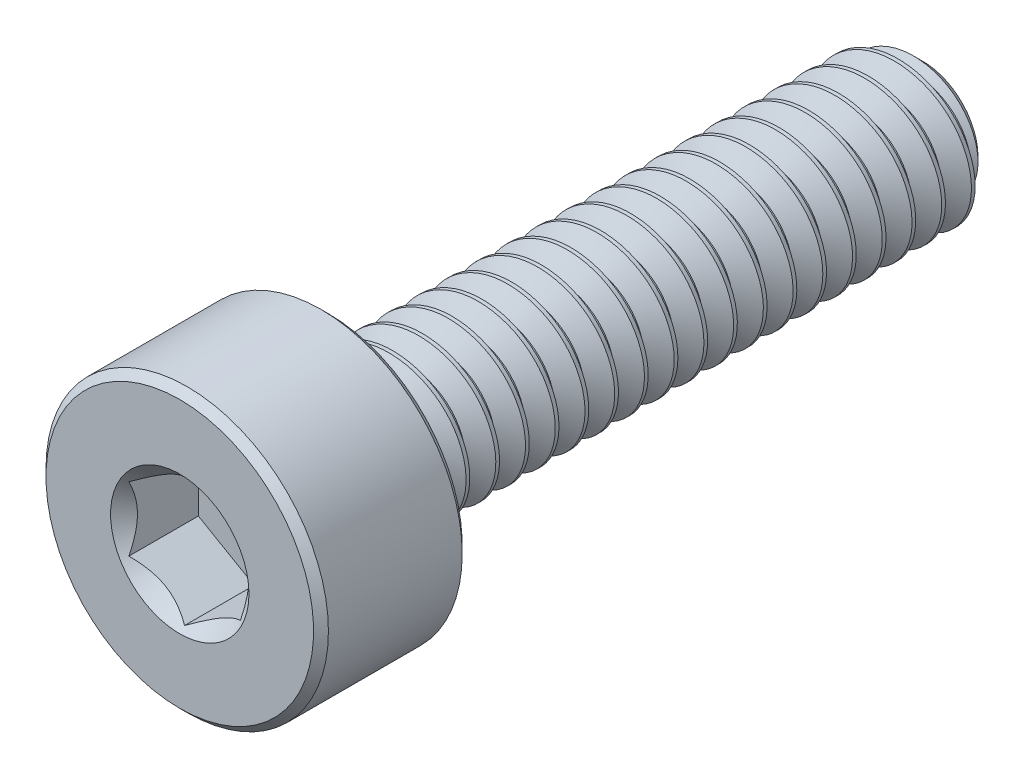
SolidWorks part; units mm, degrees
ref_plane "Front Plane" through (0, 0, 0) normal (0, 0, 1) x (1, 0, 0)
ref_plane "Top Plane" through (0, 0, 0) normal (0, 1, 0) x (1, 0, 0)
ref_plane "Right Plane" through (0, 0, 0) normal (1, 0, 0) x (0, 0, -1)
sketch "Sketch1" plane through (0, 0, 0) normal (1, 0, 0) x (0, 0, -1)
  line L0 (-5, 0) -> (5, 0) construction
  line L1 (5, 0) -> (5, 0.7402) construction
  line L2 (5, 0.7402) -> (4.7402, 1) construction
  line L3 (4.7402, 1) -> (4.7, 1) construction
  line L4 (4.7, 1) -> (-3, 1) construction
  line L5 (-3, 1) -> (-3, 1.9) construction
  line L6 (-3, 1.9) -> (-5, 1.9) construction
  line L7 (-5, 1.9) -> (-5, 0) construction
  line L8 (5, 0.7402) -> (5, 1) construction
  line L9 (4.975, 1.0433) -> (5.175, 0.6969) construction
  line L10 (5.175, 0.6969) -> (5.375, 1.0433) construction
  line L11 (5.375, 1.0433) -> (4.975, 1.0433) construction
  line L12 (5.175, 1.0433) -> (5.175, 1) construction
  line L13 (5.175, 0.6969) -> (5.175, 0.7402) construction
  line L14 (5.15, 0.7402) -> (5.2, 0.7402) construction
  line L15 (5, 1) -> (5.35, 1) construction
  line L16 (4.9875, 1.0217) -> (5.3625, 1.0217) construction
  line L17 (5, 0) -> (5, -1) construction
  line L18 (-3.1, 1.9) -> (-3, 1.8) construction
  line L19 (-4.9, 1.9) -> (-5, 1.8) construction
  line L20 (-3, 1) -> (-3, 0) construction
  line L21 (-3, 0.5) -> (-0.3333, 0.5) construction
  line L22 (-0.3333, 0.5) -> (2.3333, 0.5) construction
  line L23 (2.3333, 0.5) -> (5, 0.5) construction
  line L24 (-0.3333, 0.5) -> (-0.3333, 1) construction
  line L25 (-0.3333, 1) -> (-0.3333, 1.9) construction
  line L26 (2.3333, 0.5) -> (2.3333, 1.9) construction
  point P0 (-5, 0.75)
  point P3 (4, 1)
  point P4 (0, 0)
  point P18 (2.3333, 1)
  point P22 (5.175, 0.7402)
  point P24 (4.7, 1)
  point P25 (5.175, 1)
  point P28 (5.175, 1.0217)
  point P29 (4, -1)
  point P30 (-0.3333, 1)
  point P31 (-4, 1.9)
  point P37 (-3.35, 1.9)
  point P38 (-4.85, 1.9)
  point P45 (-0.3333, 0.5)
  point P46 (2.3333, 0.5)
  dimension "D2" = 0.05
  dimension "D7" = 0.1
  dimension "D8" = 0.1
  dimension "D9" = 0.1
  dimension "D10" = 0.05
  dimension "D11" = 0.25
  dimension "Drive Size" = 1.5
  dimension "Head Diameter" = 3.8
  dimension "Head Height" = 2
  dimension "Thread Pitch" = 0.4
  dimension "Thread Size" = 2
  dimension "Length" = 8
  dimension "D12" = 0.3
  dimension "D4" = 1
  dimension "D3" = 45
sketch "Sketch2" plane through (0, 0, 0) normal (1, 0, 0) x (0, 0, -1)
  line L0 (-5, 0) -> (-5, 1.8)
  line L1 (-4.9, 1.9) -> (-3.1, 1.9)
  line L2 (-3, 1.8) -> (-3, 1.1)
  line L4 (4.7402, 1) -> (5, 0.7402)
  line L5 (5, 0.7402) -> (5, 0)
  line L6 (-3, 1.9) -> (-5, 1.9) construction
  line L7 (5, 0) -> (-5, 0)
  line L8 (-4.9, 1.9) -> (-5, 1.8) construction
  line L10 (-4.9, 1.9) -> (-5, 1.8)
  line L14 (-3.1, 1.9) -> (-3, 1.8) construction
  line L16 (-3.1, 1.9) -> (-3, 1.8)
  line L17 (-3, 1) -> (-3, 1.9) construction
  line L19 (-2.9, 1) -> (4.7402, 1)
  line L20 (4.7, 1) -> (-3, 1) construction
  arc A1 (-3, 1.1) -> (-2.9, 1) centre (-2.9, 1.1) ccw
  dimension "D3" = 0.1
revolve "Revolve1" add sketch "Sketch2" angle 360 about L7
sketch "Sketch3" plane through (0, 0, 5) normal (0, 0, 1) x (1, 0, 0)
  line L1 (0.75, -0.433) -> (0.75, 0.433)
  line L2 (0.75, 0.433) -> (0, 0.866)
  line L3 (0, 0.866) -> (-0.75, 0.433)
  line L4 (-0.75, 0.433) -> (-0.75, -0.433)
  line L5 (-0.75, -0.433) -> (0, -0.866)
  line L6 (0, -0.866) -> (0.75, -0.433)
  circle A0 centre (0, 0) radius 0.75 construction
  circle A1 centre (0, 0) radius 1.9 construction
  circle A2 centre (0, 0) radius 1.9 construction
  circle A3 centre (0, 0) radius 0.866 construction
  point P13 (0, 0)
  dimension "D1" = 1.7321
extrude "Cut-Extrude1" cut sketch "Sketch3" against normal offset from surface (1 mm away) 1 up to face at (0, 1.8, 3)
sketch "Sketch4" plane through (0, 0, 5) normal (0, 0, 1) x (1, 0, 0)
  circle A0 centre (0, 0) radius 0.931
  dimension "D1" = 1.862
extrude "Cut-Extrude2" cut sketch "Sketch4" against normal up to vertex (1 mm away) draft 45 up to point (0, 1.9, 4)
sketch "Sketch11" plane through (0, 0, 0) normal (1, 0, 0) x (0, 0, -1)
  line L0 (-5, 0) -> (5, 0) construction
  line L1 (-5, 0) -> (5, 0) construction
  line L2 (-1.5, 0) -> (-1.5, 1) construction
  line L3 (4.7, 1) -> (-3, 1) construction
  line L4 (3.5, 0) -> (3.5, 1) construction
  line L6 (5, 0.7402) -> (5, 1) construction
  point P2 (-1.5, 0)
  point P3 (3.5, 0)
  dimension "D1" = 1.5
  dimension "D2" = 1.5
sketch "Sketch6" plane through (0, 0, -5) normal (0, 0, -1) x (-1, 0, 0)
  circle A0 centre (0, 0) radius 1
curve "Helix/Spiral1" pitch 0.4 height 8.4 radius 1 centre (0, 0, -5) axis (0, 0, 1) start towards (0, 1, 0)
sketch "Sketch10" plane through (0, 0, 0) normal (1, 0, 0) x (0, 0, -1)
  line L0 (-2.9, -1.9) -> (-2.9, 1.9)
  line L5 (-5, 0) -> (5, 0) construction
  line L6 (-2.9, 1) -> (-2.9, -1) construction
  point P3 (-2.9, 0)
split "Split1" trim tools "Sketch10" bodies to split 106 resulting bodies 114 115
sketch "Sketch7" plane through (0, 0, 0) normal (1, 0, 0) x (0, 0, -1)
  line L0 (4.9875, 1.0217) -> (5.3625, 1.0217)
  line L1 (5.3625, 1.0217) -> (5.2, 0.7402)
  line L2 (5.2, 0.7402) -> (5.15, 0.7402)
  line L3 (5.15, 0.7402) -> (4.9875, 1.0217)
sweep "Cut-Sweep1" cut profiles "Sketch7" path "Helix/Spiral1" align with end faces yes
sketch "Sketch8" plane through (0, 0, 0) normal (1, 0, 0) x (0, 0, -1)
  line L0 (-3, 0) -> (-3, 1)
  line L1 (-2.9, -1) -> (-2.9, 1) construction
  line L2 (-3, 1) -> (-2.9, 1)
  line L4 (-2.9, 1) -> (-2.3226, 0)
  line L5 (-2.3226, 0) -> (-3, 0)
  line L6 (4.7, 1) -> (-3, 1) construction
  line L7 (-5, 0) -> (5, 0) construction
  dimension "D1" = 60
revolve "Revolve2" add sketch "Sketch8" angle 360 about L5
equation "\"D2@Sketch1\" = \"Thread Pitch@Sketch1\" / 8"
equation "\"D4@Helix/Spiral1\" = \"Thread Pitch@Sketch1\""
equation "\"D7@Sketch1\" = \"Head Height@Sketch1\" * .05"
equation "\"D8@Sketch1\"=\"D7@Sketch1\""
equation "\"D9@Sketch1\"=\"D7@Sketch1\""
equation "\"D10@Sketch1\"=\"D7@Sketch1\"/2"
equation "\"D11@Sketch1\"=\"D10@Sketch1\"*5"
equation "\"D4@Sketch1\"=\"Thread Pitch@Sketch1\"*2.5"
equation "\"D12@Sketch1\"=\"Thread Pitch@Sketch1\"*.75"
equation "\"D3@Helix/Spiral1\"=\"Length@Sketch1\"+\"Thread Pitch@Sketch1\""
equation "\"D3@Sketch2\"=\"Thread Size@Sketch1\"*0.05"
equation "\"D1@Sketch11\"=\"Length@Sketch1\"*0.1875"
equation "\"D2@Sketch11\"=\"D1@Sketch11\""
equation "\"D1@Sketch4\"=\"D1@Sketch3\"*1.075"
